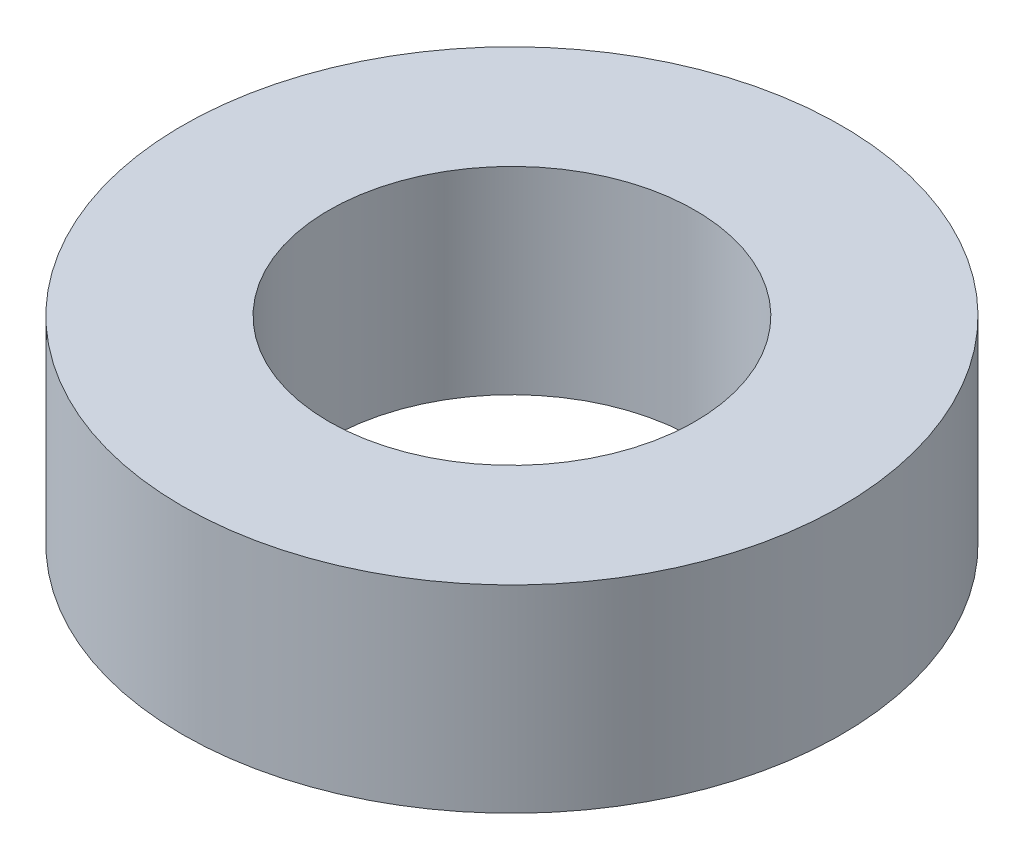
SolidWorks part; units mm, degrees
ref_plane "Front Plane" through (0, 0, 0) normal (0, 0, 1) x (1, 0, 0)
ref_plane "Top Plane" through (0, 0, 0) normal (0, 1, 0) x (1, 0, 0)
ref_plane "Right Plane" through (0, 0, 0) normal (1, 0, 0) x (0, 0, -1)
sketch "Sketch1" plane through (0, 0, 0) normal (0, 1, 0) x (1, 0, 0)
  circle A0 centre (0, 0) radius 45
  dimension "FLANGE_OD" = 90
extrude "Boss-Extrude1" add sketch "Sketch1" along normal blind 27
sketch "Sketch2" plane through (0, 0, 0) normal (0, 1, 0) x (1, 0, 0)
  circle A0 centre (0, 0) radius 25
  dimension "BORE_D" = 50
extrude "Cut-Extrude1" cut sketch "Sketch2" along normal through all
sketch "Sketch3" plane through (0, 27, 0) normal (0, 1, 0) x (1, 0, 0)
  circle A0 centre (0, 0) radius 15.4265 construction
  circle A1 centre (-15.4265, 0) radius 2.7466
  dimension "BOLT_D" = 5.4933
  dimension "BOLT_PCD" = 30.853
extrude "Cut-Extrude2" cut sketch "Sketch3" against normal blind 23.0491 rebuild error yes
pattern_circular "CirPattern1" count 8 over 360 rebuild error yes
